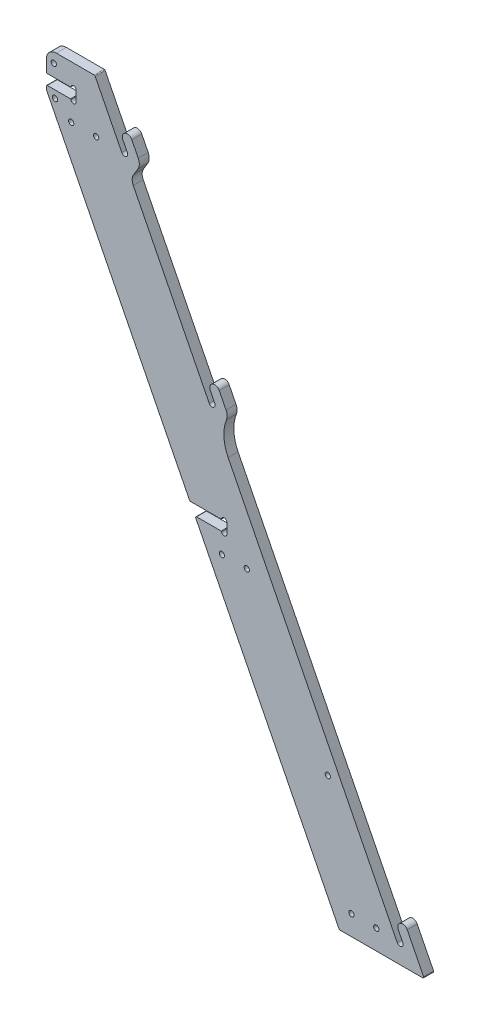
SolidWorks part; units mm, degrees
material "PE High Density"
ref_plane "Front Plane" through (0, 0, 0) normal (0, 0, 1) x (1, 0, 0)
ref_plane "Top Plane" through (0, 0, 0) normal (0, 1, 0) x (1, 0, 0)
ref_plane "Right Plane" through (0, 0, 0) normal (1, 0, 0) x (0, 0, -1)
sketch "Sketch1" plane through (0, 0, 0) normal (0, 0, 1) x (1, 0, 0)
  line L1 (0, 0) -> (-396.875, 787.4)
  line L4 (0, 0) -> (-85.332, 0)
  line L5 (-396.875, 787.4) -> (-482.207, 787.4)
  line L6 (-482.207, 787.4) -> (-85.332, 0)
  line L7 (215.9, 0) -> (215.9, 787.4) construction
  dimension "D1" = 76.2
  dimension "D2" = 787.4
  dimension "D3" = 215.9
  dimension "D4" = 612.775
extrude "Boss-Extrude1" add sketch "Sketch1" along normal blind 12.7
sketch "Sketch3" plane through (0, 0, 12.7) normal (0, 0, 1) x (1, 0, 0)
  line L0 (-85.332, 0) -> (0, 0) construction
  line L5 (-396.875, 787.4) -> (-482.207, 787.4) construction
  line L10 (-228.6, 364.871) -> (-275.832, 364.871)
  line L11 (-228.6, 364.871) -> (-228.6, 377.952)
  line L12 (-228.6, 377.952) -> (-275.832, 377.952)
  line L13 (-275.832, 364.871) -> (-275.832, 377.952)
  line L14 (215.9, 0) -> (215.9, 787.4) construction
  line L15 (-273.05, 453.0598) -> (-320.282, 453.0598) construction
  line L16 (-273.05, 453.0598) -> (-273.05, 466.1408) construction
  line L17 (-273.05, 466.1408) -> (-320.282, 466.1408) construction
  line L18 (-320.282, 453.0598) -> (-320.282, 466.1408) construction
  line L19 (-420.6875, 745.9726) -> (-467.9195, 745.9726)
  line L20 (-420.6875, 745.9726) -> (-420.6875, 759.0536)
  line L21 (-420.6875, 759.0536) -> (-467.9195, 759.0536)
  line L22 (-467.9195, 745.9726) -> (-467.9195, 759.0536)
  line L25 (-482.207, 787.4) -> (-85.332, 0) construction
  line L27 (-420.6875, 759.0536) -> (-382.5875, 759.0536) construction
  line L28 (0, 0) -> (-396.875, 787.4) construction
  line L29 (-187.325, 282.9814) -> (-234.557, 282.9814) construction
  line L30 (-187.325, 282.9814) -> (-187.325, 296.0624) construction
  line L31 (-187.325, 296.0624) -> (-234.557, 296.0624) construction
  line L32 (-234.557, 282.9814) -> (-234.557, 296.0624) construction
  line L33 (-495.3, 894.0038) -> (-542.532, 894.0038) construction
  line L34 (-495.3, 894.0038) -> (-495.3, 907.0848) construction
  line L35 (-495.3, 907.0848) -> (-542.532, 907.0848) construction
  line L36 (-542.532, 894.0038) -> (-542.532, 907.0848) construction
  line L37 (-482.207, 787.4) -> (-85.332, 0) construction
  line L38 (-228.6, 364.871) -> (-183.9068, 364.871) construction
  line L39 (0, 0) -> (-396.875, 787.4) construction
  line L40 (-420.6875, 745.9726) -> (-375.9943, 745.9726) construction
  point P5 (-296.666, 466.1408)
  point P36 (-458.7875, 759.0536)
  dimension "D2" = 13.081
  dimension "D3" = 28.3464
  dimension "D4" = 612.775
  dimension "D5" = 76.2
  dimension "D6" = 466.1408
  dimension "D7" = 745.9726
  dimension "D8" = 636.5875
  dimension "D9" = 38.1
  dimension "D10" = 488.95
  dimension "D11" = 444.5
  dimension "D12" = 711.2
  dimension "D13" = 377.952
  dimension "D14" = 81.8896
  dimension "D15" = 403.225
  dimension "D16" = 408.5983
  dimension "D17" = 835.3723
extrude "Cut-Extrude1" cut sketch "Sketch3" against normal through all
sketch "Sketch10" plane through (0, 0, 12.7) normal (0, 0, 1) x (1, 0, 0)
  line L0 (0, 0) -> (-396.875, 787.4) construction
  line L1 (-244.0247, 501.7803) -> (-249.7409, 513.1212)
  line L2 (-244.0247, 501.7803) -> (-251.1127, 498.2077) construction
  line L3 (-249.7409, 513.1212) -> (-238.4, 518.8373) construction
  line L4 (-238.4, 518.8373) -> (-226.9677, 496.1556)
  line L6 (-239.6804, 475.5259) -> (-251.1127, 498.2077)
  line L7 (0, 0) -> (-396.875, 787.4) construction
  line L8 (-226.9677, 496.1556) -> (-239.6804, 475.5259)
  line L9 (-482.207, 496.1556) -> (0, 496.1556) construction
  line L10 (-396.875, 787.4) -> (-482.207, 787.4) construction
  line L11 (-244.0247, 501.7803) -> (-232.6838, 507.4965) construction
  line L12 (-351.1457, 696.673) -> (-362.578, 719.3548)
  line L13 (-355.49, 722.9274) -> (-361.2061, 734.2682)
  line L14 (-349.8652, 739.9844) -> (-338.4329, 717.3026)
  line L15 (-338.4329, 717.3026) -> (-351.1457, 696.673)
  line L16 (0, 0) -> (-11.4323, 22.6817)
  line L17 (-4.3443, 26.2544) -> (-10.0605, 37.5952)
  line L18 (1.2804, 43.3114) -> (12.7128, 20.6296)
  line L19 (12.7128, 20.6296) -> (0, 0) construction
  line L20 (0, 0) -> (23.1108, 0)
  line L21 (23.1108, 0) -> (12.7128, 20.6296)
  line L22 (-358.3938, 742.7968) -> (-338.3872, 703.1037) construction
  line L23 (-338.3872, 703.1037) -> (-351.1457, 696.673) construction
  line L24 (-355.49, 722.9274) -> (-349.8195, 725.7854) construction
  arc A0 (-244.0247, 501.7803) -> (-251.1127, 498.2077) centre (-247.5687, 499.994) cw
  arc A1 (-249.7409, 513.1212) -> (-238.4, 518.8373) centre (-244.0704, 515.9793) cw
  arc A2 (-355.49, 722.9274) -> (-362.578, 719.3548) centre (-359.034, 721.1411) cw
  arc A3 (-361.2061, 734.2682) -> (-349.8652, 739.9844) centre (-355.5357, 737.1263) cw
  arc A4 (-4.3443, 26.2544) -> (-11.4323, 22.6817) centre (-7.8883, 24.4681) cw
  arc A5 (-10.0605, 37.5952) -> (1.2804, 43.3114) centre (-4.39, 40.4533) cw
  dimension "D1" = 7.9375
  dimension "D2" = 25.4
  dimension "D3" = 12.7
  dimension "D4" = 12.7
  dimension "D5" = 12.7
  dimension "D6" = 291.2444
  dimension "D9" = 101.6
  dimension "D10" = 349.25
  dimension "D11" = 44.45
  dimension "D12" = 19.05
  dimension "D7" = 2
  dimension "D8" = 2
extrude "Boss-Extrude3" add sketch "Sketch10" against normal up to surface (12.7 mm away) up to face at (-311.4421, 505.8749, 0)
hole_wizard "1/4 Clearance Hole1" positions "Sketch11" profile "Sketch12" hole size "1/4" standard "ANSI Inch" end condition through all
sketch "Sketch11" plane through (0, 0, 12.7) normal (0, 0, 1) x (1, 0, 0)
  line L0 (-411.0511, 780.2548) -> (-14.1761, -7.1452) construction
  line L4 (0, 0) -> (-14.1761, -7.1452)
  line L6 (-396.875, 787.4) -> (-411.0511, 780.2548)
  line L7 (-251.1127, 498.2077) -> (-351.1457, 696.673) construction
  line L8 (-427.0375, 720.5726) -> (-395.2875, 720.5726) construction
  line L10 (-420.6875, 745.9726) -> (-420.6875, 759.0536) construction
  line L11 (-461.3263, 745.9726) -> (-420.6875, 745.9726) construction
  line L12 (-420.6875, 745.9726) -> (-395.2875, 720.5726) construction
  line L13 (-395.2875, 720.5726) -> (-203.2, 339.471) construction
  line L14 (-228.6, 364.871) -> (-203.2, 339.471) construction
  line L15 (-203.2, 339.471) -> (-234.95, 339.471) construction
  line L16 (-69.85, 25.4) -> (-38.1, 25.4) construction
  line L18 (-85.332, 0) -> (23.1108, 0) construction
  line L19 (215.9, 0) -> (215.9, 787.4) construction
  point P4 (-99.9186, 162.9679)
  point P31 (-427.0375, 720.5726)
  point P40 (-395.2875, 720.5726)
  point P64 (-203.2, 339.471)
  point P67 (-234.95, 339.471)
  point P69 (-69.85, 25.4)
  point P71 (-38.1, 25.4)
  dimension "D1" = 25.4
  dimension "D2" = 15.875
  dimension "D4" = 190.5
  dimension "D5" = 25.4
  dimension "D6" = 31.75
  dimension "D7" = 254
  dimension "D8" = 25.4
sketch "Sketch12" plane through (-99.9186, 162.9679, 12.7) normal (1, 0, 0) x (0, -1, 0)
  line L0 (0, 0) -> (0, 12.7)
  line L1 (0, 12.7) -> (3.3782, 12.7)
  line L2 (3.3782, 12.7) -> (3.3782, 0)
  line L5 (3.3782, 0) -> (0, 0)
  line L11 (0, -6.35) -> (0, 107.95) construction
  dimension "Thru Hole Dia." = 6.7564
  dimension "Thru Hole Depth" = 12.7
sketch "Sketch13" plane through (0, 0, 12.7) normal (0, 0, 1) x (1, 0, 0)
  line L0 (-420.6875, 745.9726) -> (-420.6875, 759.0536) construction
  line L1 (-458.7875, 759.0536) -> (-482.207, 759.0536)
  line L2 (-458.7875, 759.0536) -> (-458.7875, 787.4)
  line L3 (-458.7875, 787.4) -> (-482.207, 787.4)
  line L4 (-482.207, 759.0536) -> (-482.207, 787.4)
  line L5 (-420.6875, 759.0536) -> (-467.9195, 759.0536) construction
  dimension "D1" = 38.1
extrude "Cut-Extrude2" cut sketch "Sketch13" against normal through all
sketch "Sketch14" plane through (0, 0, 12.7) normal (0, 0, 1) x (1, 0, 0)
  line L0 (-420.6875, 759.0536) -> (-458.7875, 759.0536) construction
  line L1 (-461.3263, 745.9726) -> (-420.6875, 745.9726) construction
  line L2 (-228.6, 377.952) -> (-275.832, 377.952) construction
  line L3 (-269.2388, 364.871) -> (-228.6, 364.871) construction
  circle A0 centre (-424.1165, 759.0536) radius 3.429
  circle A1 centre (-424.1165, 745.9726) radius 3.429
  circle A2 centre (-232.029, 377.952) radius 3.429
  circle A3 centre (-232.029, 364.871) radius 3.429
  dimension "D1" = 6.858
extrude "Cut-Extrude3" cut sketch "Sketch14" against normal through all
fillet "Fillet4" radius 50.8 1 edges at (-239.6804, 475.5259, 6.35)
fillet "Fillet5" radius 12.7 4 edges at (-226.9677, 496.1556, 6.35) (-338.4329, 717.3026, 6.35) (-351.1457, 696.673, 6.35) (-458.7875, 787.4, 6.35)
fillet "Fillet6" radius 1.27 3 edges at (-458.7875, 759.0536, 6.35) (-275.832, 377.952, 6.35) (-269.2388, 364.871, 6.35)
fillet "Fillet7" radius 0.508 4 edges at (-235.458, 364.871, 6.35) (-235.458, 377.952, 6.35) (-427.5455, 759.0536, 6.35) (-427.5455, 745.9726, 6.35)
sketch "Sketch15" plane through (0, 0, 12.7) normal (0, 0, 1) x (1, 0, 0)
  line L0 (-458.7875, 760.3236) -> (-458.7875, 774.7) construction
  line L3 (-396.875, 787.4) -> (-446.0875, 787.4) construction
  point P2 (-447.675, 736.6)
  point P5 (-449.2625, 774.7)
  dimension "D1" = 12.7
  dimension "D2" = 38.1
  dimension "D3" = 11.1125
  dimension "D4" = 9.525
hole_wizard "1/4 Clearance Hole2" positions "Sketch16" profile "Sketch17" hole size "1/4" standard "ANSI Inch" end condition through all
sketch "Sketch16" plane through (0, 0, 12.7) normal (0, 0, 1) x (1, 0, 0)
  point P8 (-447.675, 736.6)
  point P10 (-449.2625, 774.7)
sketch "Sketch17" plane through (-447.675, 736.6, 12.7) normal (1, 0, 0) x (0, -1, 0)
  line L0 (0, 0) -> (0, 12.7)
  line L1 (0, 12.7) -> (3.3782, 12.7)
  line L2 (3.3782, 12.7) -> (3.3782, 0)
  line L5 (3.3782, 0) -> (0, 0)
  line L11 (0, -6.35) -> (0, 107.95) construction
  dimension "Thru Hole Dia." = 6.7564
  dimension "Thru Hole Depth" = 12.7
sketch "Sketch18" plane through (0, 0, 12.7) normal (0, 0, 1) x (1, 0, 0)
  line L0 (-458.7875, 745.9726) -> (-458.7875, 740.9356)
  line L1 (-461.3263, 745.9726) -> (-428.0206, 745.9726) construction
  line L2 (-461.3263, 745.9726) -> (-276.1841, 378.6504) construction
  line L3 (-458.7875, 740.9356) -> (-461.3263, 745.9726)
  line L4 (-461.3263, 745.9726) -> (-458.7875, 745.9726)
  line L5 (-458.7875, 760.3236) -> (-458.7875, 774.7) construction
extrude "Cut-Extrude4" cut sketch "Sketch18" against normal through all
fillet "Fillet8" radius 1.27 5 edges at (-458.7875, 740.9356, 6.35) (-458.7875, 745.9726, 6.35) (-396.875, 787.4, 6.35) (23.1108, 0, 6.35) (-85.332, 0, 6.35)
